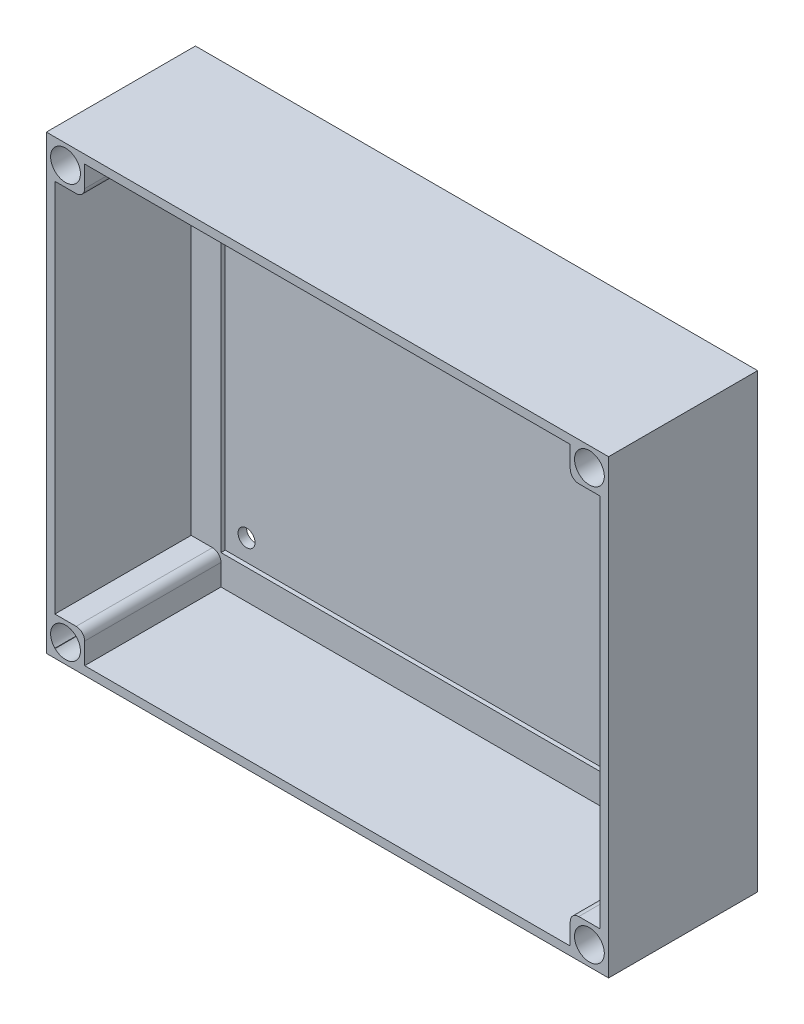
SolidWorks part; units mm, degrees
ref_plane "Plan de face" through (0, 0, 0) normal (0, 0, 1) x (1, 0, 0)
ref_plane "Plan de dessus" through (0, 0, 0) normal (0, 1, 0) x (1, 0, 0)
ref_plane "Plan de droite" through (0, 0, 0) normal (1, 0, 0) x (0, 0, -1)
sketch "Esquisse1" plane through (0, 0, 0) normal (0, 0, 1) x (1, 0, 0)
  line L0 (43, 78) -> (43, 88)
  line L1 (0, 0) -> (114, 0)
  line L2 (0, 0) -> (0, 88)
  line L3 (0, 88) -> (114, 88)
  line L4 (114, 0) -> (114, 88)
  line L6 (43, 84.301) -> (43, 78)
  line L7 (43, 78) -> (63, 78)
  line L8 (63, 84.301) -> (63, 78)
  line L9 (43, 88) -> (63, 88)
  line L10 (63, 88) -> (63, 84.301)
  line L12 (-9, 97) -> (123, 97)
  line L13 (-9, 97) -> (-9, -9)
  line L14 (-9, -9) -> (123, -9)
  line L15 (123, 97) -> (123, -9)
  circle A0 centre (5, 83) radius 2
  circle A1 centre (109, 83) radius 2
  circle A2 centre (5, 5) radius 2
  circle A3 centre (109, 5) radius 2
  dimension "D5" = 4
  dimension "D6" = 4
  dimension "D9" = 4
  dimension "D12" = 4
  dimension "D1" = 114
  dimension "D2" = 88
  dimension "D3" = 5
  dimension "D4" = 5
  dimension "D7" = 5
  dimension "D8" = 5
  dimension "D10" = 5
  dimension "D11" = 5
  dimension "D13" = 5
  dimension "D14" = 5
  dimension "D15" = 43
  dimension "D16" = 63
  dimension "D17" = 10
  dimension "D18" = 132
  dimension "D19" = 9
  dimension "D20" = 106
  dimension "D21" = 9
extrude "Boss.-Extru.1" add sketch "Esquisse1" along normal blind 2 contours L3 L10 L8 L7 L0 L2 L1 L4 A3 A2 A1 A0 region at (57.0818, 43.2026, 0)
extrude "Boss.-Extru.2" add sketch "Esquisse1<3>" along normal blind 3 contours L15 L12 L13 L14 L4 L1 L2 L3 region at (57, 95.3071, 0)
sketch "Esquisse1<3>" plane through (0, 0, 0) normal (0, 0, 1) x (1, 0, 0) same geometry as "Esquisse1"
sketch "Esquisse2" plane through (0, 0, 3) normal (0, 0, 1) x (1, 0, 0)
  line L0 (114, -9) -> (123, -9)
  line L1 (-9, 97) -> (123, 97)
  line L2 (-9, 97) -> (-9, -9)
  line L3 (-9, -9) -> (123, -9)
  line L4 (123, 97) -> (123, -9)
  line L5 (-7, 95) -> (121, 95)
  line L6 (-7, 95) -> (-7, -7)
  line L7 (-7, -7) -> (121, -7)
  line L8 (121, 95) -> (121, -7)
  line L9 (-9, -9) -> (0, -9)
  line L10 (-9, -9) -> (-9, 0)
  line L11 (-9, 0) -> (0, 0)
  line L12 (0, -9) -> (0, 0)
  line L13 (114, -9) -> (114, 0)
  line L14 (114, 0) -> (123, 0)
  line L15 (123, -9) -> (123, 0)
  line L16 (114, 88) -> (123, 88)
  line L17 (114, 88) -> (114, 97)
  line L18 (114, 97) -> (123, 97)
  line L19 (123, 88) -> (123, 97)
  line L20 (-9, 88) -> (0, 88)
  line L21 (-9, 88) -> (-9, 97)
  line L22 (-9, 97) -> (0, 97)
  line L23 (0, 88) -> (0, 97)
  circle A0 centre (-4.5, -4.5) radius 3.5
  circle A1 centre (118.5, -4.5) radius 3.5
  circle A2 centre (118.5, 92.5) radius 3.5
  circle A3 centre (-4.5, 92.5) radius 3.5
  line M25 (123, -9) -> (123, 97)
  line M26 (123, 97) -> (-9, 97)
  line M27 (-9, 97) -> (-9, -9)
  line M28 (-9, -9) -> (123, -9)
  dimension "D5" = 7
  dimension "D1" = 2
  dimension "D2" = 2
  dimension "D3" = 2
  dimension "D4" = 2
  dimension "D6" = 4.5
  dimension "D7" = 4.5
sketch "Esquisse3" plane through (0, 0, 35) normal (0, 0, 1) x (1, 0, 0)
  line L5 (-9, 97) -> (123, 97) construction
  line L6 (-9, 97) -> (-9, -9) construction
  line L7 (123, 97) -> (123, -9) construction
  line L8 (-9, -9) -> (123, -9) construction
  circle A0 centre (-4.5, 92.5) radius 3.5
  circle A1 centre (118.5, 92.5) radius 3.5
  circle A2 centre (118.5, -4.5) radius 3.5
  circle A3 centre (-4.5, -4.5) radius 3.5
  point P4 (0, 0)
  dimension "D1" = 7
  dimension "D4" = 7
  dimension "D9" = 7
  dimension "D12" = 7
  dimension "D2" = 4.5
  dimension "D3" = 4.5
  dimension "D5" = 4.5
  dimension "D6" = 4.5
  dimension "D7" = 4.5
  dimension "D8" = 4.5
  dimension "D10" = 4.5
  dimension "D11" = 4.5
extrude "Boss.-Extru.4" add sketch "Esquisse2" along normal blind 32 contours A3 L5 L23 L20 L6 M26 M27 | L5 A3 L6 | L5 A3 | L6 A3 | A3 L6 L20 L23 L5 | L23 L5 L17 L1 | A2 L5 L8 L16 L17 M25 M26 | A2 L5 L17 L16 L8 | L8 A2 L5 | L8 A2 | L5 A2 | L16 L8 L14 L4 | A1 L7 L13 L14 L8 M28 M25 | A1 L8 L14 L13 L7 | L8 A1 L7 | L8 A1 | L7 A1 | L3 L13 L7 L12 | A0 L6 L11 L2 L12 L7 M28 | A0 L7 L12 L11 L6 | L6 A0 L7 | L6 A0 | L7 A0 | L20 L2 L11 L6 region at (114.1273, -8, 3) region at (57, -8, 3) region at (-4.5, -8.8727, 3) region at (114.099, -3.5, 3) region at (122, 44, 3) region at (-1.0253, -6.901, 3) region at (118.1913, -4.1913, 3) region at (118.5, -7.4053, 3) region at (122, 88.1273, 3) region at (-8, 44, 3) region at (-4.5, -7.4053, 3) region at (-4.1913, -4.1913, 3) region at (121.4053, -4.5, 3) region at (117.5, 88.099, 3) region at (-8.8727, 92.5, 3) region at (57, 96, 3) region at (118.1913, 92.1913, 3) region at (121.4053, 92.5, 3) region at (-6.901, 89.0253, 3) region at (-7.4053, -4.5, 3) region at (118.5, 95.4053, 3) region at (-7.4053, 92.5, 3) region at (-4.1913, 92.1913, 3) region at (-4.5, 95.4053, 3)
extrude "Enlèv. mat.-Extru.1" cut sketch "Esquisse3" against normal blind 5
fillet "Congé1" radius 2 4 edges at (114, 0, 19) (0, 0, 19) (0, 88, 19) (114, 88, 19)
